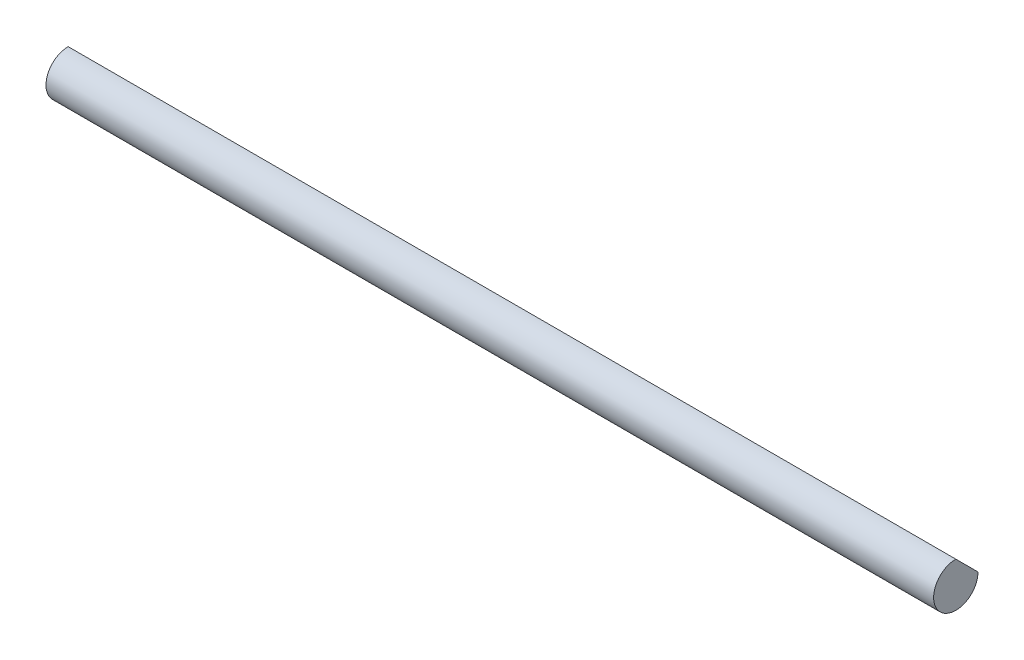
SolidWorks part; units mm, degrees
ref_plane "Front Plane" through (0, 0, 0) normal (0, 0, 1) x (1, 0, 0)
ref_plane "Top Plane" through (0, 0, 0) normal (0, 1, 0) x (1, 0, 0)
ref_plane "Right Plane" through (0, 0, 0) normal (1, 0, 0) x (0, 0, -1)
sketch "Sketch1" plane through (0, 0, 0) normal (1, 0, 0) x (0, 0, -1)
  line L0 (0, 3.175) -> (3.175, 0)
  arc A0 (0, 3.175) -> (3.175, 0) centre (0, 0) ccw
  dimension "D1" = 6.35
extrude "Boss-Extrude1" add sketch "Sketch1" along normal blind 127
ref_axis "Axis1" through (0, 0, 0) along (1, 0, 0)
